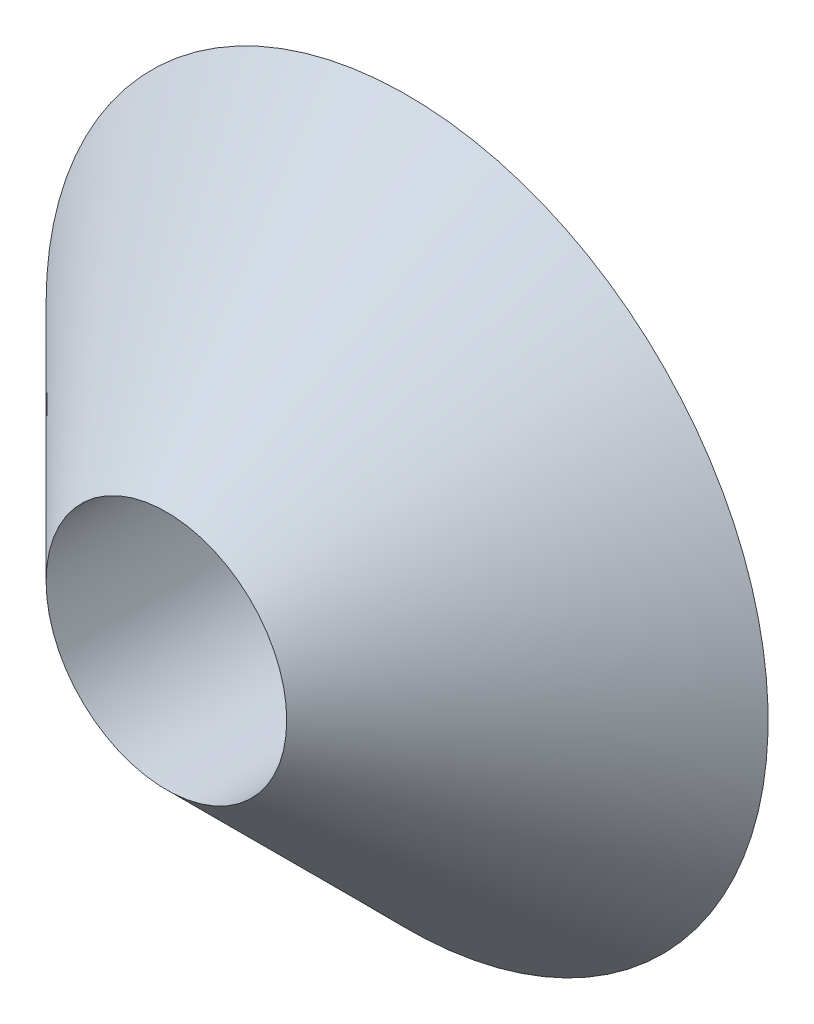
SolidWorks part; units mm, degrees
ref_plane "Front Plane" through (0, 0, 0) normal (0, 0, 1) x (1, 0, 0)
ref_plane "Top Plane" through (0, 0, 0) normal (0, 1, 0) x (1, 0, 0)
ref_plane "Right Plane" through (0, 0, 0) normal (1, 0, 0) x (0, 0, -1)
sketch "Sketch1" plane through (0, 0, 0) normal (0, 1, 0) x (1, 0, 0)
  line L0 (0, 0) -> (-5, 0)
  line L1 (0, 0) -> (0, 10)
  line L2 (0, 10) -> (-15, 10)
  line L3 (-15, 10) -> (-5, 0)
  dimension "D1" = 15
  dimension "D2" = 5
  dimension "D3" = 10
revolve "Revolve1" add sketch "Sketch1" angle 360 about L1
sketch "Sketch14" plane through (0, 0, 0) normal (0, 0, 1) x (1, 0, 0)
  circle A0 centre (0, 0) radius 5
  dimension "D1" = 10
extrude "Cut-Extrude1" cut sketch "Sketch14" against normal through all contours A0
